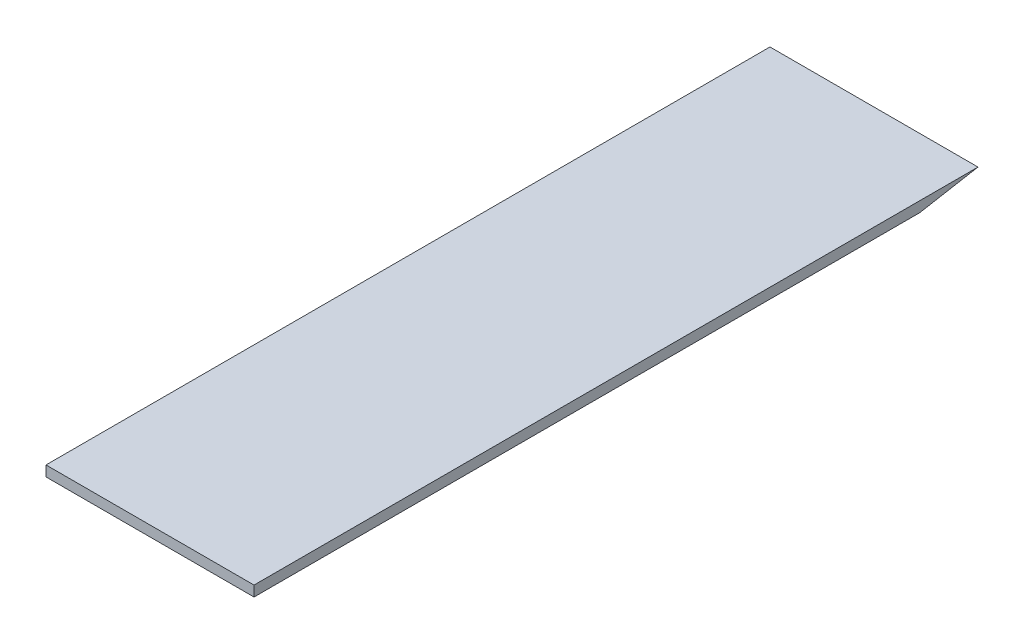
SolidWorks part; units mm, degrees
ref_plane "Front Plane" through (0, 0, 0) normal (0, 0, 1) x (1, 0, 0)
ref_plane "Top Plane" through (0, 0, 0) normal (0, 1, 0) x (1, 0, 0)
ref_plane "Right Plane" through (0, 0, 0) normal (1, 0, 0) x (0, 0, -1)
sketch "Sketch1" plane through (0, 0, 0) normal (1, 0, 0) x (0, 0, -1)
  line L19 (0, 5) -> (0, 0)
  line L20 (0, 0) -> (320, 0)
  line L21 (320, 0) -> (348, 5)
  line L37 (0, 5) -> (348, 5)
  dimension "D1" = 5
  dimension "D8" = 28
  dimension "D9" = 320
extrude "Boss-Extrude1" add sketch "Sketch1" along normal blind 100 contours L19 L20 L21 L37
